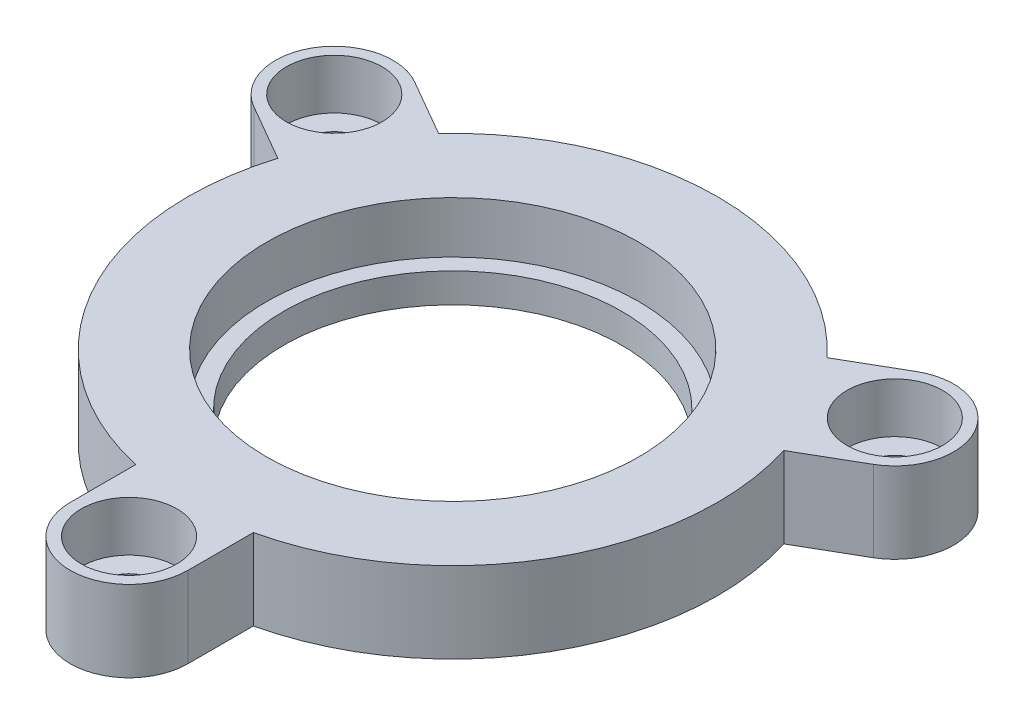
SolidWorks part; units mm, degrees
ref_plane "Front Plane" through (0, 0, 0) normal (0, 0, 1) x (1, 0, 0)
ref_plane "Top Plane" through (0, 0, 0) normal (0, 1, 0) x (1, 0, 0)
ref_plane "Right Plane" through (0, 0, 0) normal (1, 0, 0) x (0, 0, -1)
sketch "Sketch1" plane through (0, 0, 0) normal (0, 1, 0) x (1, 0, 0)
  line L0 (4, -22) -> (4, -17.5499)
  line L1 (-4, -22) -> (-4, -17.5499)
  line L2 (-21.0526, 7.5359) -> (-17.1987, 5.3109)
  line L3 (-17.0526, 14.4641) -> (-13.1987, 12.2391)
  line L4 (17.0526, 14.4641) -> (13.1987, 12.2391)
  line L5 (21.0526, 7.5359) -> (17.1987, 5.3109)
  circle A0 centre (0, 0) radius 18
  circle A1 centre (0, 0) radius 11.5
  circle A2 centre (0, -22) radius 4
  circle A3 centre (0, -22) radius 2.1 construction
  circle A4 centre (0, 0) radius 12.65
  circle A5 centre (-19.0526, 11) radius 2.1 construction
  circle A6 centre (-19.0526, 11) radius 4
  circle A7 centre (19.0526, 11) radius 2.1 construction
  circle A8 centre (19.0526, 11) radius 4
  point P28 (0, 0)
  dimension "D2" = 36
  dimension "D3" = 23
  dimension "D4" = 4.2
  dimension "D5" = 8
  dimension "D6" = 25.3
  dimension "D1" = 22
  dimension "D7" = 3
extrude "Boss-Extrude1" add sketch "Sketch1" along normal blind 5.5 contours A2 L0 A0 | A2 A0 L1 | A2 A3 | A6 A5 | A6 A0 L3 | A6 L2 A0 | A8 A7 | A8 A0 L5 | A8 L4 A0 | A1 | A0 region at (3.0911, 0, 18.7412) region at (0, 0, 22) region at (-3.0911, 0, 18.7412) region at (17.7759, 0, -6.6936) region at (-17.7759, 0, -6.6936) region at (19.0526, 0, -11) region at (14.6848, 0, -12.0476) region at (-19.0526, 0, -11) region at (-14.6848, 0, -12.0476) region at (0, 0, 0)
extrude "Cut-Extrude1" cut sketch "Sketch1<3>" against normal blind 3.5 from surface contours A4 starting at face at (0, 5.5, 0)
sketch "Sketch1<3>" plane through (0, 0, 0) normal (0, 1, 0) x (1, 0, 0) same geometry as "Sketch1"
hole_wizard "CBORE for M3 Hex Socket Head Cap Screw1" positions "Sketch2" profile "Sketch4" counterbore size "M3" standard "ISO"
sketch "Sketch2" plane through (0, 5.5, 0) normal (0, 1, 0) x (1, 0, 0)
  point P0 (-19.0526, 11)
  point P3 (19.0526, 11)
  point P6 (0, -22)
sketch "Sketch4" plane through (-19.0526, 5.5, -11) normal (1, 0, 0) x (0, 0, 1)
  line L0 (0, 0) -> (0, 46.0215)
  line L1 (0, 46.0215) -> (1.7, 45)
  line L2 (1.7, 45) -> (1.7, 3.4)
  line L3 (1.7, 3.4) -> (3.25, 3.4)
  line L4 (3.25, 3.4) -> (3.25, 0)
  line L5 (3.25, 0) -> (0, 0)
  line L10 (0, 46.0215) -> (-1.7, 45) construction
  line L11 (0, -6.35) -> (0, 107.95) construction
  dimension "Hole Dia." = 3.4
  dimension "Hole Depth" = 45
  dimension "C'Bore Dia." = 6.5
  dimension "C'Bore Depth" = 3.4
  dimension "Drill Angle" = 118
